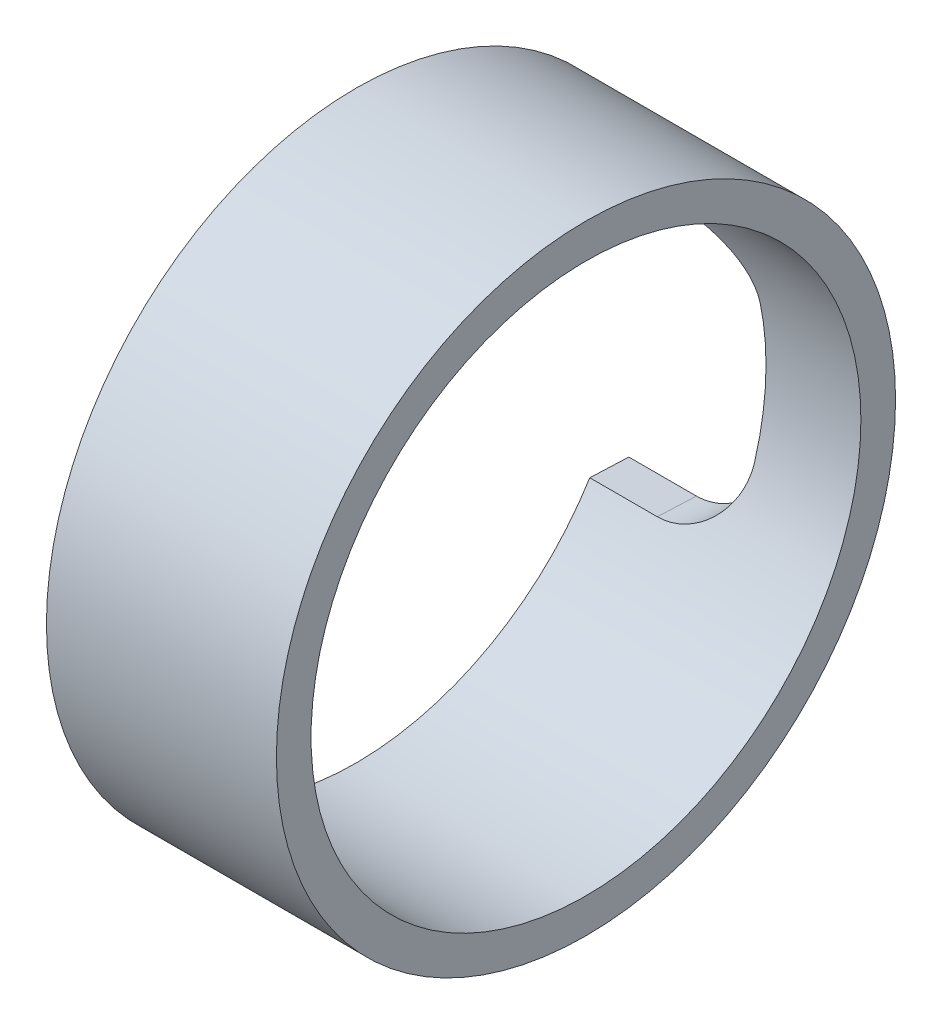
SolidWorks part; units mm, degrees
material "Nylon 6/10"
ref_plane "Front Plane" through (0, 0, 0) normal (0, 0, 1) x (1, 0, 0)
ref_plane "Top Plane" through (0, 0, 0) normal (0, 1, 0) x (1, 0, 0)
ref_plane "Right Plane" through (0, 0, 0) normal (1, 0, 0) x (0, 0, -1)
sketch "Sketch1" plane through (0, 0, 0) normal (0, 0, 1) x (1, 0, 0)
  line L0 (-31.75, 7.5) -> (-48.665, 7.5) construction
  line L1 (-45.363, 8.7312) -> (-38.877, 8.7312)
  line L2 (-45.363, 8.7312) -> (-45.363, 7.754)
  line L3 (-45.363, 7.754) -> (-38.877, 7.754)
  line L4 (-38.877, 8.7312) -> (-38.877, 7.754)
  line L5 (-45.49, 7.7355) -> (-45.49, 12.5132) construction
  line L6 (-38.75, 15.2446) -> (-38.75, -15.2446) construction
  line L7 (0, 0) -> (-47.1489, 0) construction
  dimension "D1" = 0.254
  dimension "D2" = 0.127
  dimension "D3" = 0.127
  dimension "D4" = 17.4625
revolve "Revolve1" add sketch "Sketch1" angle 360 about L7
ref_plane "Plane1" through (0, 0, 0) normal (0, -0.0407, -0.9992) x (1, 0, 0)
sketch "Sketch3" plane through (0, 0, 0) normal (0, -0.0407, -0.9992) x (1, 0, 0)
  line L0 (-45.363, 3.81) -> (-45.363, -3.81)
  line L1 (-45.363, 7.754) -> (-45.363, -7.754) construction
  line L2 (-45.363, -3.81) -> (-43.458, -3.81)
  line L3 (-41.553, -1.905) -> (-41.553, 1.905)
  line L4 (-43.458, 3.81) -> (-45.363, 3.81)
  line L5 (-45.363, 8.7312) -> (-45.363, -8.7312) construction
  line L6 (-45.363, 8.7312) -> (-45.363, -8.7312) construction
  line L7 (-41.553, 0) -> (-45.363, 0) construction
  arc A0 (-43.458, -3.81) -> (-41.553, -1.905) centre (-43.458, -1.905) ccw
  arc A1 (-41.553, 1.905) -> (-43.458, 3.81) centre (-43.458, 1.905) ccw
  dimension "D1" = 7.62
  dimension "D2" = 3.81
extrude "Cut-Extrude1" cut sketch "Sketch3" along normal up to next
